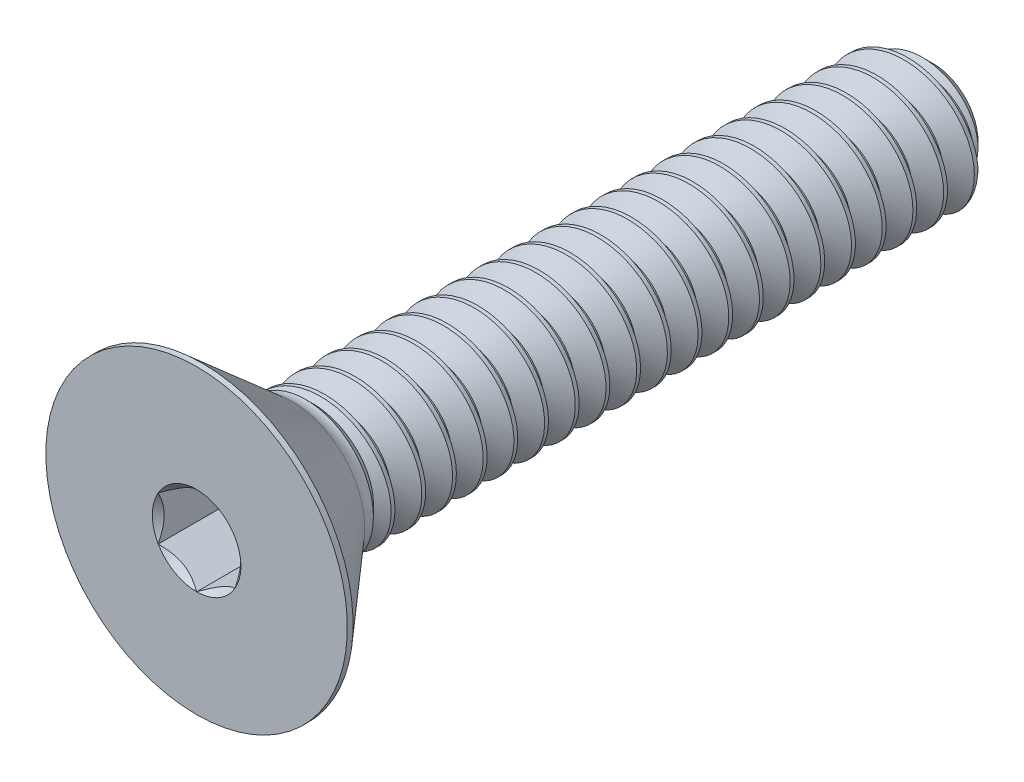
SolidWorks part; units mm, degrees
ref_plane "Front" through (0, 0, 0) normal (0, 0, 1) x (1, 0, 0)
ref_plane "Top" through (0, 0, 0) normal (0, 1, 0) x (1, 0, 0)
ref_plane "Right" through (0, 0, 0) normal (1, 0, 0) x (0, 0, -1)
sketch "Sketch1" plane through (0, 0, 0) normal (1, 0, 0) x (0, 0, -1)
  line L0 (-9.525, 3.8989) -> (-9.3772, 3.8989) construction
  line L1 (-9.3772, 3.8989) -> (-7.0612, 1.8857) construction
  line L2 (-9.525, 1.7526) -> (9.525, 1.7526)
  line L3 (9.525, 1.7526) -> (9.525, 0)
  line L4 (9.525, 0) -> (-9.525, 0)
  line L5 (-9.525, 0) -> (-9.525, 3.8989) construction
  line L6 (-9.525, 3.8989) -> (-9.525, -3.8989) construction
  line L7 (9.525, 1.7526) -> (9.525, -1.7526) construction
  line L8 (-9.525, -3.8989) -> (-9.3772, -3.8989) construction
  line L9 (-9.3772, -3.8989) -> (-7.0612, -1.8857) construction
  line L11 (-9.525, 1.7526) -> (-9.525, 0)
  line L12 (-6.7053, 1.7526) -> (-6.7053, 0) construction
  line L14 (9.525, -1.7526) -> (8.7312, -1.7526) construction
  line L15 (-9.525, 0.9922) -> (-9.525, -0.9922)
  arc A1 (-7.0612, 1.8857) -> (-6.7053, 1.7526) centre (-6.7053, 2.295) ccw construction
  point P18 (0, 0)
  point P19 (8.3344, -1.7526)
  point P24 (-9.525, 0)
  dimension "Head Diameter" = 7.7978
  dimension "Thread OD" = 3.5052
  dimension "Head Height" = 2.4638
  dimension "D1" = 0.1478
  dimension "Countersink Angle" = 82
  dimension "Thread Pitch" = 0.7937
  dimension "D2" = 1.1906
  dimension "Drive Size" = 1.9844
sketch "Sketch12" plane through (0, 0, 0) normal (1, 0, 0) x (0, 0, -1)
  line L0 (9.525, 1.7526) -> (9.525, 0) construction
  line L1 (-9.525, 1.7526) -> (9.525, 1.7526) construction
  line L2 (-9.525, 1.7526) -> (-9.525, 0) construction
  line L3 (9.525, 0) -> (-9.525, 0) construction
  line L4 (9.525, 1.7526) -> (9.525, 0)
  line L5 (-9.525, 1.7526) -> (9.525, 1.7526)
  line L6 (-9.525, 1.7526) -> (-9.525, 0)
  line L7 (9.525, 0) -> (-9.525, 0)
revolve "Revolve3" add sketch "Sketch12" angle 360 about L7
sketch "Sketch3" plane through (0, 0, -9.525) normal (0, 0, -1) x (-1, 0, 0)
  circle A0 centre (0, 0) radius 1.7526
sketch "Sketch7" plane through (0, 0, 0) normal (1, 0, 0) x (0, 0, -1)
  line L0 (-9.525, 3.8989) -> (-9.3772, 3.8989) construction
  line L1 (-9.3772, 3.8989) -> (-7.0612, 1.8857) construction
  line L2 (-9.525, 3.8989) -> (-9.3772, 3.8989)
  line L3 (-9.3772, 3.8989) -> (-7.0612, 1.8857)
  line L4 (-6.7053, 1.7526) -> (-6.7053, 0) construction
  line L5 (-6.7053, 1.7526) -> (-6.7053, 0)
  line L7 (-9.525, 0) -> (-9.525, 3.8989) construction
  line L8 (-9.525, 0) -> (-9.525, 3.8989)
  line L9 (-9.525, 0) -> (-6.7053, 0)
  line L10 (16.5964, 0) -> (-16.5964, 0) construction
  arc A0 (-7.0612, 1.8857) -> (-6.7053, 1.7526) centre (-6.7053, 2.295) ccw construction
  arc A1 (-7.0612, 1.8857) -> (-6.7053, 1.7526) centre (-6.7053, 2.295) ccw
revolve "Revolve2" add sketch "Sketch7" angle 360 mid plane about L9
ref_plane "Plane1" through (0, 0, 6.7053) normal (0, 0, 1) x (1, 0, 0)
sketch "Sketch8" plane through (0, 0, 6.7053) normal (0, 0, 1) x (1, 0, 0)
  circle A0 centre (0, 0) radius 1.7526
extrude "Boss-Extrude1" add sketch "Sketch8" against normal through all draft 46
chamfer "Chamfer1" distance 0.5953 angle 45 1 edges at (0, 1.7526, -9.525)
sketch "Sketch5" plane through (0, 0, 9.525) normal (0, 0, 1) x (1, 0, 0)
  line L0 (0, 0) -> (-1.1457, 0) construction
  line L1 (0, 0) -> (-2.7496, 1.5875) construction
  line L2 (0, 0) -> (-2.7496, -1.5875) construction
  line L6 (0, 1.1457) -> (0, 0.9449) construction
  line L7 (0, 0.9449) -> (0, 0.7441) construction
  line L9 (0, 1.1457) -> (-0.9922, 0.5728)
  line L10 (-0.9922, 0.5728) -> (-0.9922, -0.5728)
  line L11 (-0.9922, -0.5728) -> (0, -1.1457)
  line L12 (0, -1.1457) -> (0.9922, -0.5728)
  line L13 (0.9922, -0.5728) -> (0.9922, 0.5728)
  line L14 (0.9922, 0.5728) -> (0, 1.1457)
  circle A0 centre (0, 0) radius 1.1457 construction
  circle A1 centre (0, 0) radius 0.9449 construction
  circle A2 centre (0, 0) radius 0.7441 construction
  circle A3 centre (0, 0) radius 0.9922 construction
  dimension "D3" = 1.4883
  dimension "D4" = 30
  dimension "D5" = 30
  dimension "Hex" = 1.9844
extrude "Cut-Extrude2" cut sketch "Sketch5" against normal blind 1.7247
sketch "Sketch6" plane through (0, 0, 9.525) normal (0, 0, 1) x (1, 0, 0)
  circle A0 centre (0, 0) radius 1.1457
extrude "Cut-Extrude3" cut sketch "Sketch6" against normal blind 1.7247 draft 45
ref_plane "Plane3" through (0, 0, 6.7053) normal (0, 0, 1) x (1, 0, 0)
split "Split1" trim tools "Plane3" bodies to split 135 resulting bodies 133 134
curve "Helix/Spiral1" pitch 0.7937 height 19.05 turns 24
sketch "Sketch2" plane through (0, 0, 0) normal (1, 0, 0) x (0, 0, -1)
  line L0 (9.525, 1.7526) -> (10.2195, 1.7526)
  line L1 (10.2195, 1.7526) -> (9.9219, 1.237)
  line L2 (9.9219, 1.237) -> (9.8227, 1.237)
  line L3 (9.8227, 1.237) -> (9.525, 1.7526)
  line L4 (9.6738, 1.4948) -> (10.0707, 1.4948) construction
  dimension "D1" = 60
  dimension "D2" = 0.0992
  dimension "D3" = 0.3969
sweep "Cut-Sweep1" cut profiles "Sketch2" path "Helix/Spiral1"
sketch "Sketch13" plane through (0, 0, 6.7053) normal (0, 0, 1) x (1, 0, 0)
  circle A0 centre (0, 0) radius 1.7526 construction
  circle A1 centre (0, 0) radius 1.7526
extrude "Boss-Extrude3" add sketch "Sketch13" against normal up to next (16.2303 mm away) draft 45
equation "\"D3@Helix/Spiral1\" = \"Length@Sketch1\""
equation "\"D2@Sketch2\" = \"D4@Helix/Spiral1\" * .125"
equation "\"D3@Sketch2\" = \"D4@Helix/Spiral1\" * .5"
equation "\"D1@Chamfer1\" = \"D4@Helix/Spiral1\" * .75"
equation "\"D1@Cut-Extrude2\" = \"Head Height@Sketch1\" * .7"
equation "\"D1@Cut-Extrude3\" = \"D1@Cut-Extrude2\""
equation "\"D3@Sketch5\" = \"Hex@Sketch5\" * .75"
equation "\"D2@Sketch1\" = \"Thread Pitch@Sketch1\" * 1.5"
equation "\"D4@Helix/Spiral1\"=\"Thread Pitch@Sketch1\""
equation "\"Hex@Sketch5\"=\"Drive Size@Sketch1\""
equation "\"D1@Sketch1\"=\"Head Height@Sketch1\"*.06"
